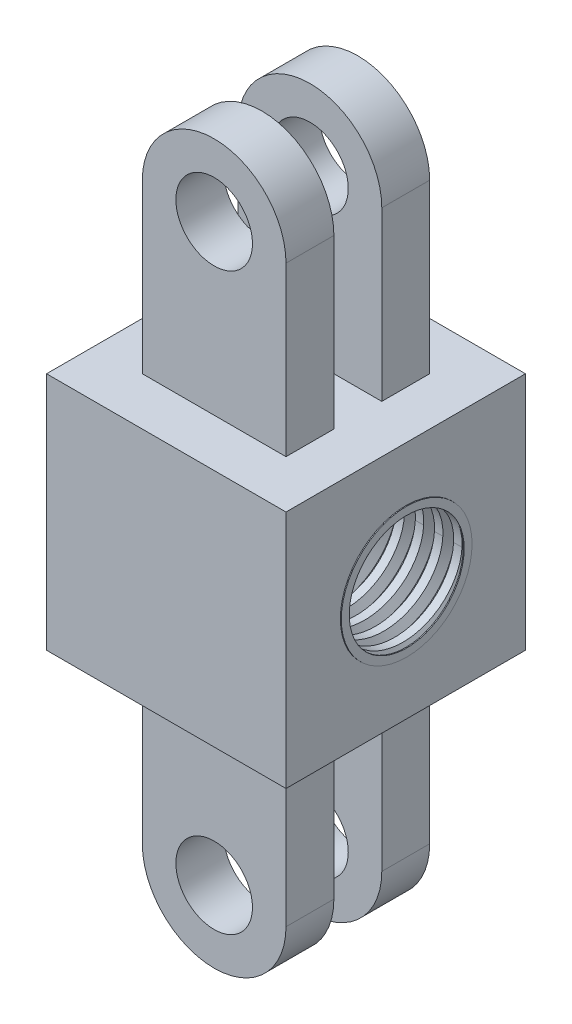
SolidWorks part; units mm, degrees
ref_plane "Front Plane" through (0, 0, 0) normal (0, 0, 1) x (1, 0, 0)
ref_plane "Top Plane" through (0, 0, 0) normal (0, 1, 0) x (1, 0, 0)
ref_plane "Right Plane" through (0, 0, 0) normal (1, 0, 0) x (0, 0, -1)
sketch "Sketch1" plane through (0, 0, 0) normal (0, 1, 0) x (1, 0, 0)
  line L1 (0, 0) -> (25, 0)
  line L2 (0, 0) -> (0, -25)
  line L3 (0, -25) -> (25, -25)
  line L4 (25, 0) -> (25, -25)
  dimension "D1" = 25
  dimension "D2" = 25
extrude "Boss-Extrude1" add sketch "Sketch1" along normal blind 25
sketch "Sketch2" plane through (0, 25, 0) normal (0, 1, 0) x (1, 0, 0)
  line L0 (0, -12.5) -> (48.3049, -12.5) construction
  line L1 (0, 0) -> (0, -25) construction
  line L2 (25, 0) -> (0, 0) construction
  line L3 (5, -5) -> (20, -5)
  line L4 (5, -5) -> (5, -10)
  line L5 (5, -10) -> (20, -10)
  line L6 (20, -5) -> (20, -10)
  line L9 (20, -20) -> (20, -15)
  line L10 (5, -15) -> (20, -15)
  line L11 (5, -20) -> (5, -15)
  line L12 (5, -20) -> (20, -20)
  dimension "D1" = 5
  dimension "D2" = 5
  dimension "D3" = 5
  dimension "D4" = 15
extrude "Boss-Extrude2" add sketch "Sketch2" along normal blind 17.5
sketch "Sketch3" plane through (0, 0, 20) normal (0, 0, 1) x (1, 0, 0)
  line L0 (5, 42.5) -> (20, 42.5) construction
  circle A0 centre (12.5, 42.5) radius 7.5
  circle A1 centre (12.5, 42.5) radius 4
  dimension "D1" = 8
extrude "Boss-Extrude4" add sketch "Sketch3" against normal up to surface (5 mm away) up to face at (12.5, 33.75, 15)
sketch "Sketch4" plane through (0, 0, 20) normal (0, 0, 1) x (1, 0, 0)
  line L0 (8.5, 42.5) -> (16.5, 42.5) construction
  circle A0 centre (12.5, 42.5) radius 4
extrude "Cut-Extrude1" cut sketch "Sketch4" against normal blind 21.5
sketch "Sketch5" plane through (0, 0, 5) normal (0, 0, -1) x (-1, 0, 0)
  line L0 (-8.5, 42.5) -> (-5, 42.5) construction
  line L1 (-20, 42.5) -> (-16.5, 42.5) construction
  line L2 (-8.5, 42.5) -> (-5, 42.5)
  line L3 (-20, 42.5) -> (-16.5, 42.5)
  circle A0 centre (-12.5, 42.5) radius 4 construction
  arc A1 (-5, 42.5) -> (-20, 42.5) centre (-12.5, 42.5) ccw construction
  circle A2 centre (-12.5, 42.5) radius 4
  arc A3 (-5, 42.5) -> (-20, 42.5) centre (-12.5, 42.5) ccw
  line M1 (-5, 42.5) -> (-8.5, 42.5)
  line M3 (-16.5, 42.5) -> (-20, 42.5)
extrude "Boss-Extrude5" add sketch "Sketch5" against normal up to surface (5 mm away) contours A3 A2 M1 M3 region at (12.5, 46.6677, 5) up to face at (12.5, 36, 10)
ref_plane "Plane1" through (0, 12.5, 0) normal (0, 1, 0) x (1, 0, 0)
mirror "Mirror1" about plane through (0, 12.5, 0) normal (0, 1, 0) of "Boss-Extrude5", "Cut-Extrude1", "Boss-Extrude4", "Boss-Extrude2", "Boss-Extrude1"
sketch "Sketch6" plane through (25, 0, 0) normal (1, 0, 0) x (0, 0, -1)
  line L0 (-25, 0) -> (0, 0) construction
  line L1 (0, 25) -> (0, 0) construction
  circle A0 centre (-12.5, 12.5) radius 6
  dimension "D3" = 12
  dimension "D1" = 12.5
  dimension "D2" = 12.5
extrude "Cut-Extrude2" cut sketch "Sketch6" against normal blind 63.5
thread "Thread2" pitch 1.5 method cut profile "Thread Profile3" start angle 0, offset 2, length 30, pitch 2, diameter 12
ref_plane "Plane4" through (27, 12.5, 18.5) normal (0, -1, 0) x (0, 0, 1)
sketch "Thread Profile3" plane through (27, 12.5, 18.5) normal (0, -1, 0) x (0, 0, 1)
  line L0 (0, 0) -> (0, 1.5) construction
  line L1 (0, 0) -> (0.8119, 0.4687)
  line L2 (0.8119, 0.4687) -> (0.8119, 0.6562)
  line L3 (0.8119, 0.6562) -> (0, 1.125)
  line L4 (0.8119, 0.5625) -> (0, 0.5625) construction
  line L11 (0, 0) -> (0, 1.125)
  point P2 (0, 0)
  dimension "Pitch" = 1.5
  dimension "Profile_Angle" = 60
  dimension "Profile_Land" = 0.1875
  dimension "Profile_Height" = 0.8119
sketch "Sketch7" plane through (25, 0, 0) normal (1, 0, 0) x (0, 0, -1)
  circle A0 centre (-12.5, 12.5) radius 6
  circle A1 centre (-12.5, 12.5) radius 6.8257
extrude "Boss-Extrude6" add sketch "Sketch7" along normal blind 0.1
scale "Scale1" scale about centroid uniform scaling yes scale factor 0.7
